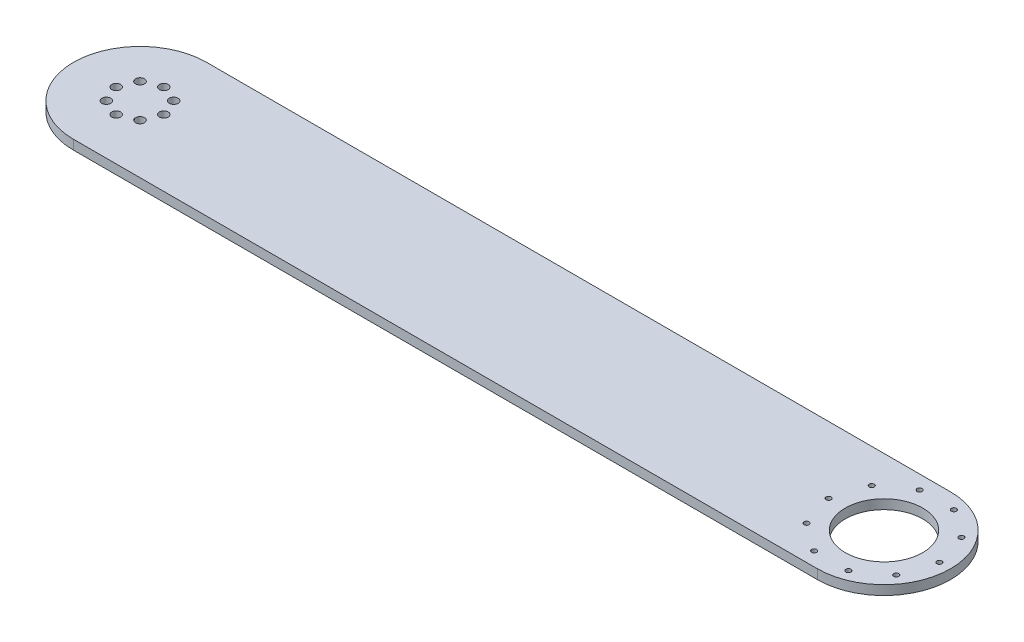
SolidWorks part; units mm, degrees
ref_plane "Front Plane" through (0, 0, 0) normal (0, 0, 1) x (1, 0, 0)
ref_plane "Top Plane" through (0, 0, 0) normal (0, 1, 0) x (1, 0, 0)
ref_plane "Right Plane" through (0, 0, 0) normal (1, 0, 0) x (0, 0, -1)
sketch "Sketch1" plane through (0, 0, 0) normal (0, 1, 0) x (1, 0, 0)
  line L0 (0, 0) -> (500, 0) construction
  line L1 (0, 44.75) -> (500, 44.75)
  line L2 (0, -44.75) -> (500, -44.75)
  arc A0 (0, 44.75) -> (0, -44.75) centre (0, 0) ccw
  arc A1 (500, -44.75) -> (500, 44.75) centre (500, 0) ccw
  circle A2 centre (0, 0) radius 16 construction
  circle A3 centre (-16, 0) radius 3
  circle A4 centre (-11.3137, 11.3137) radius 3
  circle A5 centre (0, 16) radius 3
  circle A6 centre (11.3137, 11.3137) radius 3
  circle A7 centre (16, 0) radius 3
  circle A8 centre (11.3137, -11.3137) radius 3
  circle A27 centre (500, 0) radius 37.25 construction
  circle A28 centre (537.25, 0) radius 1.7
  circle A29 centre (500, 0) radius 37.25 construction
  circle A30 centre (537.25, 0) radius 1.7
  circle A31 centre (530.1359, -21.895) radius 1.7
  circle A32 centre (511.5109, -35.4269) radius 1.7
  circle A33 centre (488.4891, -35.4269) radius 1.7
  circle A34 centre (469.8641, -21.895) radius 1.7
  circle A35 centre (462.75, 0) radius 1.7
  circle A36 centre (469.8641, 21.895) radius 1.7
  circle A37 centre (488.4891, 35.4269) radius 1.7
  circle A38 centre (511.5109, 35.4269) radius 1.7
  circle A39 centre (530.1359, 21.895) radius 1.7
  circle A40 centre (500, 0) radius 26
  circle A41 centre (0, -16) radius 3
  circle A42 centre (-11.3137, -11.3137) radius 3
  point P3 (250, 0)
  point P25 (0, 0)
  point P52 (500, 0)
  point P61 (500, 0)
  dimension "D3" = 32
  dimension "D4" = 6
  dimension "D2" = 74.5
  dimension "D7" = 3.4
  dimension "D8" = 3.4
  dimension "D10" = 52
  dimension "D1" = 500
  dimension "D6" = 7.5
  dimension "D5" = 8
  dimension "D9" = 10
extrude "Boss-Extrude1" add sketch "Sketch1" along normal blind 6.35 contours L2 A1 L1 A0 A40 A39 A38 A37 A36 A35 A34 A33 A32 A31 A28 A8 A7 A6 A5 A4 A3 region at (239.7722, 0, 0)
equation "\"L1L\"=500"
equation "\"D1@Sketch1\"=\"L1L\""
equation "\"L1Thick\"=6.35"
equation "\"D1@Boss-Extrude1\"=\"L1Thick\""
equation "\"Harm-Drive-Outer\"=74.5"
equation "\"D2@Sketch1\"=\"Harm-Drive-Outer\""
